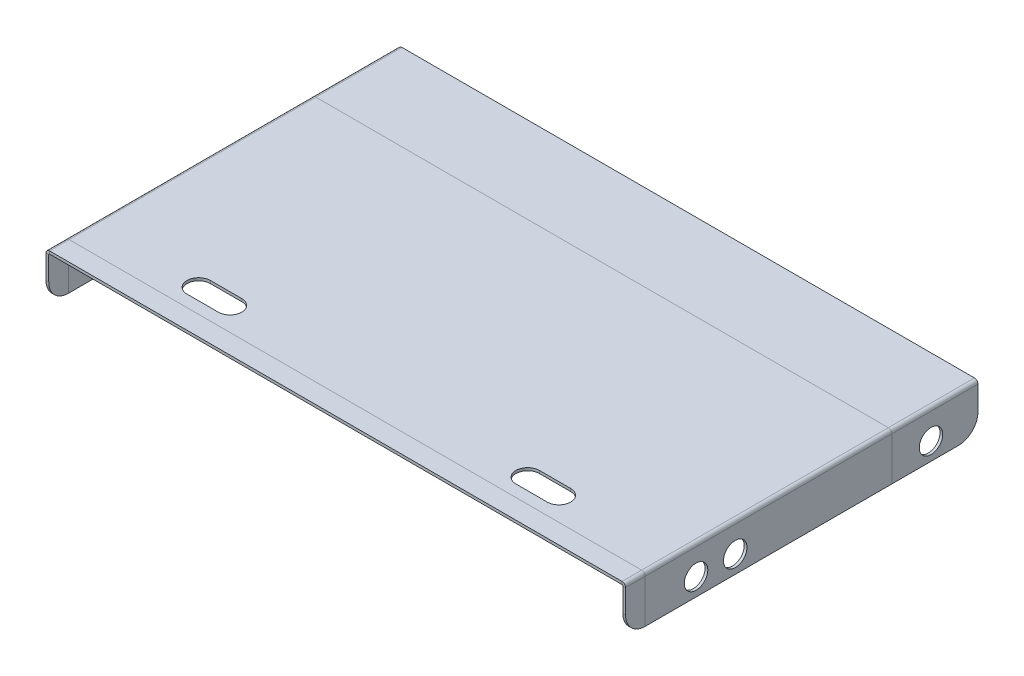
SolidWorks part; units mm, degrees
note: The reader was unsure of these and kept them because the rebuilt part matched: flange length of "边线-法兰1".
material "1023 碳钢板 (SS)"
ref_plane "前视基准面" through (0, 0, 0) normal (0, 0, 1) x (1, 0, 0)
ref_plane "上视基准面" through (0, 0, 0) normal (0, 1, 0) x (1, 0, 0)
ref_plane "右视基准面" through (0, 0, 0) normal (1, 0, 0) x (0, 0, -1)
sketch "草图1" plane through (0, 0, 0) normal (0, 1, 0) x (1, 0, 0)
  line L0 (-46, -34) -> (-38, -34) construction
  line L1 (-74, 45) -> (74, 45)
  line L2 (-74, 45) -> (-74, -45)
  line L3 (-74, -45) -> (74, -45)
  line L4 (74, 45) -> (74, -45)
  line L5 (-74, 45) -> (74, -45) construction
  line L6 (-74, -45) -> (74, 45) construction
  line L7 (-46, -31) -> (-38, -31)
  line L8 (-46, -37) -> (-38, -37)
  line L9 (38, -34) -> (46, -34) construction
  line L10 (38, -31) -> (46, -31)
  line L11 (38, -37) -> (46, -37)
  arc A0 (-46, -31) -> (-46, -37) centre (-46, -34) ccw
  arc A1 (-38, -37) -> (-38, -31) centre (-38, -34) ccw
  arc A2 (38, -31) -> (38, -37) centre (38, -34) ccw
  arc A3 (46, -37) -> (46, -31) centre (46, -34) ccw
  point P0 (0, 0)
  point P8 (-42, -34)
  point P13 (42, -34)
  point P20 (-42, -37)
  dimension "D7" = 28
  dimension "D8" = 28
  dimension "D1" = 148
  dimension "D2" = 90
  dimension "D3" = 8
  dimension "D4" = 8
  dimension "D5" = 6
  dimension "D6" = 6
  dimension "D9" = 8
base flange "基体-法兰1" sketch "草图1" thickness 0.7 reverse thickness direction no parameters "D1"=0.2
edge flange "边线-法兰1" sketch "草图12" flange profiles "草图12", "草图13" flange angle 90 flange length 12 flange position material inside bend radius 0.2 thickness 0.7 relief rectangular parameters "D6"=10, "D8"=1
sketch "草图12" plane through (74, -0.7, 0) normal (1, 0, 0) x (0, 0, 1)
  line L2 (-45, 0) -> (-45, 11.3)
  line L3 (-45, 11.3) -> (45, 11.3)
  line L4 (45, 11.3) -> (45, 0)
  line L7 (45, 0) -> (-45, 0) construction
  line L8 (45, 0) -> (-45, 0)
  line L9 (45, -0.7) -> (-45, -0.7) construction
  circle A0 centre (-33, 6.8) radius 3
  circle A1 centre (17, 6.8) radius 3
  circle A2 centre (27, 6.8) radius 3
  dimension "D1" = 6
  dimension "D2" = 4.5
  dimension "D3" = 12
  dimension "D4" = 50
  dimension "D5" = 7.5
  dimension "D6" = 10
sketch "草图13" plane through (-74, -0.7, 0) normal (-1, 0, 0) x (0, 0, -1)
  line L2 (-45, 0) -> (-45, 11.3)
  line L3 (-45, 11.3) -> (45, 11.3)
  line L4 (45, 11.3) -> (45, 0)
  line L7 (45, 0) -> (-45, 0) construction
  line L8 (45, 0) -> (-45, 0)
bend "边线折弯1" bend radius 0.2 bend angle 90 parameters "D5"=1
bend "边线折弯2" bend radius 0.2 bend angle 90 parameters "D5"=2
fillet "圆角2" radius 5 4 edges at (73.65, -12, -45) (73.65, -12, 45) (-73.65, -12, 45) (-73.65, -12, -45)
sketch "草图15" plane through (-74, 0, 0) normal (-1, 0, 0) x (0, 0, 1)
  circle A0 centre (-33, -7.5) radius 3
  circle A1 centre (17, -7.5) radius 3
  circle A2 centre (27, -7.5) radius 3
  dimension "D1" = 6
  dimension "D2" = 10
  dimension "D3" = 50
extrude "切除-拉伸1" cut sketch "草图15" against normal blind 10
sketch "草图17" plane through (0, 0, 0) normal (0, 1, 0) x (1, 0, 0)
  line L0 (-74, 23) -> (74, 23)
  line L1 (-74, 45) -> (-74, -45) construction
  line L2 (74, -45) -> (74, 45) construction
  line L3 (-73.1, -45) -> (73.1, -45) construction
  line L4 (-74, -40) -> (74, -40)
  line L5 (74, 45) -> (74, -45) construction
  dimension "D1" = 68
  dimension "D2" = 63
split "分割1" trim tools "草图17" bodies to split 109 resulting bodies 113 114 115
sketch "折弯-线1" [suppressed] plane through (0, 0, 0) normal (0, 1, 0) x (1, 0, 0)
sketch "边界框1" [suppressed] plane through (0, 0, 0) normal (0, 1, 0) x (1, 0, 0)
sheet metal parameters "钣金6" thickness 0.7 parameters "D1"=0.2
flat pattern "平板型式6" [suppressed]
sketch "折弯-线2" plane through (0, 0, 0) normal (0, 1, 0) x (1, 0, 0)
sketch "边界框2" [suppressed] plane through (0, 0, 0) normal (0, 1, 0) x (1, 0, 0)
sheet metal parameters "钣金7" thickness 0.7 parameters "D1"=0.2
flat pattern "平板型式6" [suppressed]
sketch "折弯-线2" plane through (0, 0, 0) normal (0, 1, 0) x (1, 0, 0)
sketch "边界框2" [suppressed] plane through (0, 0, 0) normal (0, 1, 0) x (1, 0, 0)
bend of the flat pattern "展平-<边线折弯1>1"
bend of the flat pattern "展平-<边线折弯2>1"
sheet metal parameters "钣金9" thickness 0.7 parameters "D1"=0.2
flat pattern "平板型式6"
sketch "折弯-线2" plane through (0, 0, 0) normal (0, 1, 0) x (1, 0, 0)
  line L0 (-74, 45) -> (-74, -45) construction
  line L1 (74, -45) -> (74, 45) construction
  line L2 (-74, 45) -> (-74, -45) construction
  line L3 (74, -45) -> (74, 45) construction
sketch3d "边界框2" [suppressed]
  line L0 (-86, -45, 0) -> (86, -45, 0) construction
  line L1 (-86, 45, 0) -> (86, 45, 0) construction
  line L2 (-86, -45, 0) -> (-86, 45, 0) construction
  line L3 (86, -45, 0) -> (86, 45, 0) construction
bend of the flat pattern "展平-<边线折弯1>1"
bend of the flat pattern "展平-<边线折弯2>1"
sheet metal parameters "钣金13" thickness 0.7 parameters "D1"=0.2
flat pattern "平板型式13" [suppressed]
sketch "折弯-线3" plane through (0, 0, 0) normal (0, 1, 0) x (1, 0, 0)
sketch "边界框3" [suppressed] plane through (0, 0, 0) normal (0, 1, 0) x (1, 0, 0)
bend of the flat pattern "展平-<边线折弯2>2"
bend of the flat pattern "展平-<边线折弯1>2"
sheet metal parameters "钣金14" thickness 0.7 parameters "D1"=0.2
flat pattern "平板型式14" [suppressed]
sketch "折弯-线4" plane through (0, 0, 0) normal (0, 1, 0) x (1, 0, 0)
sketch "边界框4" [suppressed] plane through (0, 0, 0) normal (0, 1, 0) x (1, 0, 0)
bend of the flat pattern "展平-<边线折弯2>3"
bend of the flat pattern "展平-<边线折弯1>3"
sheet metal parameters "钣金15" thickness 0.7 parameters "D1"=0.2
flat pattern "平板型式15" [suppressed]
sketch "折弯-线5" plane through (0, 0, 0) normal (0, 1, 0) x (1, 0, 0)
sketch "边界框5" [suppressed] plane through (0, 0, 0) normal (0, 1, 0) x (1, 0, 0)
bend of the flat pattern "展平-<边线折弯2>4"
bend of the flat pattern "展平-<边线折弯1>4"
